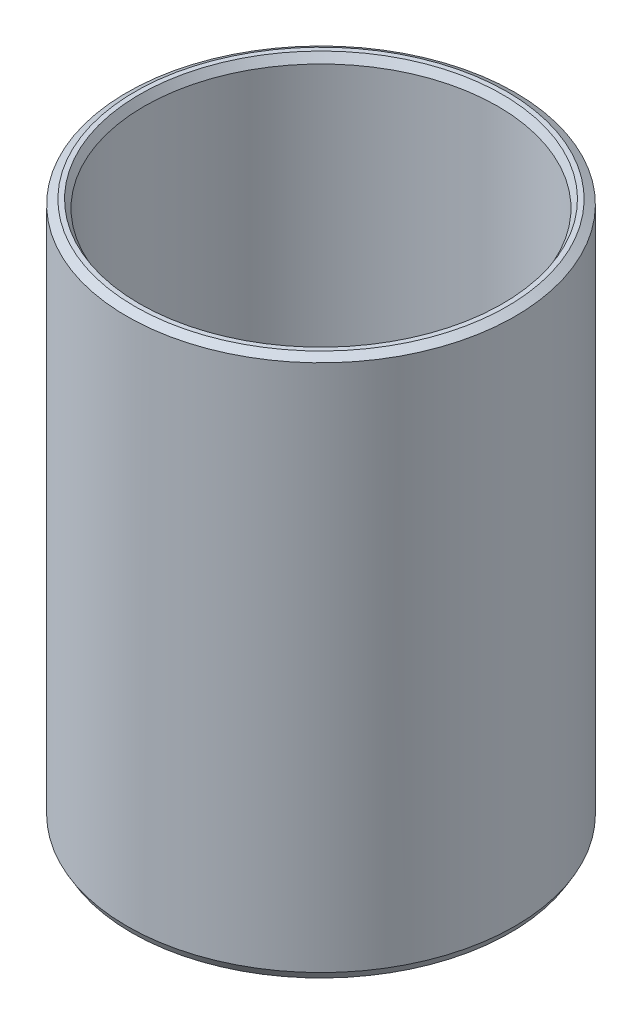
SolidWorks part; units mm, degrees
ref_plane "Front Plane" through (0, 0, 0) normal (0, 0, 1) x (1, 0, 0)
ref_plane "Top Plane" through (0, 0, 0) normal (0, 1, 0) x (1, 0, 0)
ref_plane "Right Plane" through (0, 0, 0) normal (1, 0, 0) x (0, 0, -1)
sketch "Sketch1" plane through (0, 0, 0) normal (0, 1, 0) x (1, 0, 0)
  circle A0 centre (0, 0) radius 50
  dimension "SLEEVE_OD" = 100
extrude "Boss-Extrude1" add sketch "Sketch1" along normal blind 139.3156
sketch "Sketch2" plane through (0, 0, 0) normal (0, 1, 0) x (1, 0, 0)
  circle A0 centre (0, 0) radius 45.5549
  dimension "BORE_D" = 91.1098
extrude "Cut-Extrude1" cut sketch "Sketch2" along normal through all
chamfer "Chamfer1" distance 1.1845 angle 60 4 edges at (0, 139.3156, 45.5549) (0, 0, 45.5549) (0, 0, 50) (0, 139.3156, 50) first distance on face at (0, 139.3156, 45.5549) first distance on face at (0, 0, 45.5549) first distance on face at (0, 139.3156, 50)
